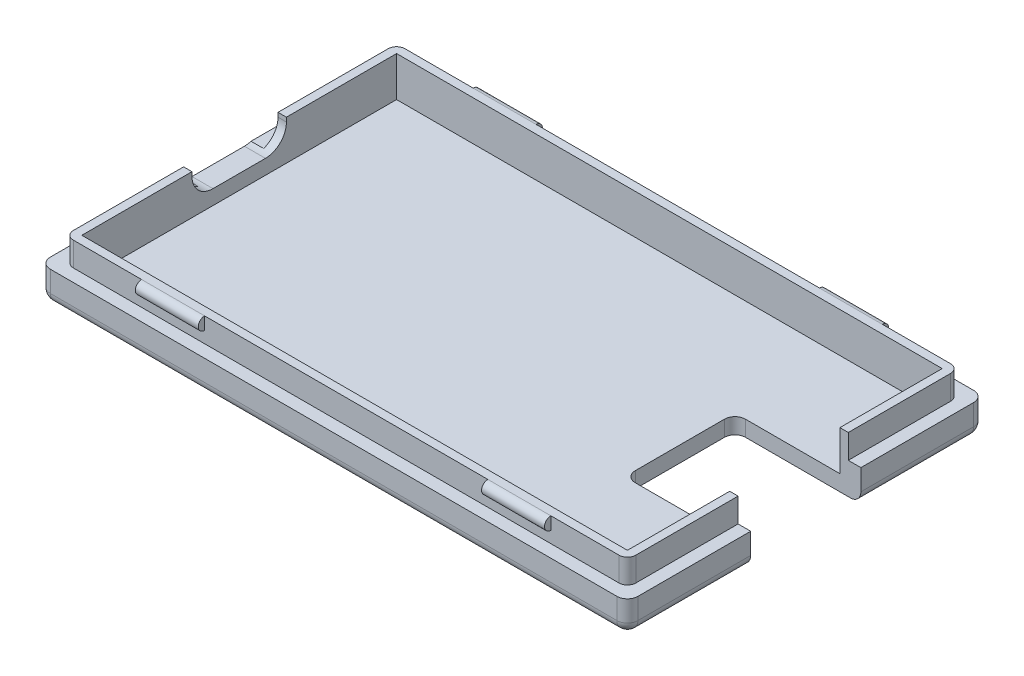
SolidWorks part; units mm, degrees
material "ABS"
ref_plane "Front Plane" through (0, 0, 0) normal (0, 0, 1) x (1, 0, 0)
ref_plane "Top Plane" through (0, 0, 0) normal (0, 1, 0) x (1, 0, 0)
ref_plane "Right Plane" through (0, 0, 0) normal (1, 0, 0) x (0, 0, -1)
sketch "Sketch1" plane through (0, 0, 0) normal (0, 1, 0) x (1, 0, 0)
  line L1 (28, -17) -> (-28, -17)
  line L2 (28, -17) -> (28, 17)
  line L3 (28, 17) -> (-28, 17)
  line L4 (-28, -17) -> (-28, 17)
  line L5 (28, -17) -> (-28, 17) construction
  line L6 (28, 17) -> (-28, -17) construction
  line L7 (26, -15) -> (-26, -15)
  line L8 (26, -15) -> (26, 15)
  line L9 (26, 15) -> (-26, 15)
  line L10 (-26, -15) -> (-26, 15)
  line L11 (26, -15) -> (-26, 15) construction
  line L12 (26, 15) -> (-26, -15) construction
  point P0 (0, 0)
  point P6 (0, 0)
  dimension "D1" = 56
  dimension "D2" = 34
  dimension "D3" = 2
  dimension "D4" = 2
extrude "Base" add sketch "Sketch1" along normal blind 1.5 contours L10 L7 L8 L9 | L4 L1 L2 L3 L7 L10 L9 L8 region at (0, 0, 16.3449) region at (0, 0, 0)
extrude "Boss-Extrude2" add sketch "Sketch1<3>" along normal blind 3 contours L4 L1 L2 L3 L7 L10 L9 L8 region at (0, 0, 16.3449)
sketch "Sketch1<3>" plane through (0, 0, 0) normal (0, 1, 0) x (1, 0, 0) same geometry as "Sketch1"
sketch "Sketch2" plane through (0, 3, 0) normal (0, 1, 0) x (1, 0, 0)
  line L0 (26, 15) -> (26, -15) construction
  line L1 (-26, -15) -> (26, -15) construction
  line L2 (-26, -15) -> (-26, 15) construction
  line L3 (-26, 15) -> (26, 15) construction
  line L4 (26, 15) -> (26, -15)
  line L5 (-26, -15) -> (26, -15)
  line L6 (-26, -15) -> (-26, 15)
  line L7 (-26, 15) -> (26, 15)
  line L8 (-26.8, 15.8) -> (26.8, 15.8)
  line L9 (26.8, 15.8) -> (26.8, -15.8)
  line L10 (-26.8, -15.8) -> (26.8, -15.8)
  line L11 (-26.8, -15.8) -> (-26.8, 15.8)
  dimension "D1" = 0.8
extrude "Wall" add sketch "Sketch2" along normal blind 2.3
sketch "Sketch3" plane through (0, 3, 0) normal (0, 1, 0) x (1, 0, 0)
  line L0 (-28, -17) -> (-28, 17) construction
  line L1 (-28, -10.25) -> (-26.8, -10.25)
  line L2 (-28, -10.25) -> (-28, -6.5)
  line L3 (-28, -6.5) -> (-26.8, -6.5)
  line L4 (-26.8, -10.25) -> (-26.8, -6.5)
  line L5 (-26.8, 15.8) -> (-26.8, -15.8) construction
  line L6 (0, 0) -> (-10.9883, 0) construction
  line L7 (-28, 6.5) -> (-26.8, 6.5)
  line L8 (-26.8, 10.25) -> (-26.8, 6.5)
  line L9 (-28, 10.25) -> (-26.8, 10.25)
  line L10 (-28, 10.25) -> (-28, 6.5)
  dimension "D1" = 13
  dimension "D2" = 20.5
extrude "GrooveForOpen" cut sketch "Sketch3" against normal blind 1
sketch "Sketch4" plane through (0, 0, 0) normal (1, 0, 0) x (0, 0, -1)
  line L0 (15.8, 5.3) -> (15.8, 3) construction
  line L1 (-15.8, 5.3) -> (-15.8, 3) construction
  circle A0 centre (15.8, 4.7) radius 0.6
  circle A1 centre (-15.8, 4.7) radius 0.6
  dimension "D1" = 1.2
extrude "LockPins" add sketch "Sketch4" along normal blind 6 from offset 13.5
mirror "LockPins2" about plane through (0, 0, 0) normal (1, 0, 0) of "LockPins"
fillet "FilletBase" radius 1 8 edges at (0, 0, 17) (28, 0, 0) (0, 0, -17) (-28, 0, 0) (28, 1.5, 17) (-28, 1.5, 17) (-28, 1.5, -17) (28, 1.5, -17)
fillet "FilletInner" radius 0.8 4 edges at (26.8, 4.15, 15.8) (-26.8, 4.15, 15.8) (-26.8, 4.15, -15.8) (26.8, 4.15, -15.8)
sketch "Sketch5" plane through (0, 0, 0) normal (1, 0, 0) x (0, 0, -1)
  line L0 (-15, 5.3) -> (15, 5.3) construction
  line L1 (-4.5, 9.6229) -> (4.5, 9.6229)
  line L2 (-4.5, 9.6229) -> (-4.5, 4.9)
  line L3 (-2.5, 2.9) -> (2.5, 2.9)
  line L4 (4.5, 9.6229) -> (4.5, 4.9)
  arc A0 (2.5, 2.9) -> (4.5, 4.9) centre (2.5, 4.9) ccw
  arc A1 (-4.5, 4.9) -> (-2.5, 2.9) centre (-2.5, 4.9) ccw
  point P4 (0, 9.6229)
  dimension "D2" = 2
  dimension "D1" = 9
  dimension "D3" = 2.4
extrude "CutCable" cut sketch "Sketch5" against normal through all
sketch "Sketch7" plane through (0, 0, 0) normal (0, -1, 0) x (1, 0, 0)
  line L0 (28, 16) -> (28, -16) construction
  line L1 (32.0379, -5.25) -> (17, -5.25)
  line L2 (32.0379, -5.25) -> (32.0379, 5.25)
  line L3 (32.0379, 5.25) -> (17, 5.25)
  line L4 (16, -4.25) -> (16, 4.25)
  line L5 (32.0379, -5.25) -> (16, 5.25) construction
  line L6 (32.0379, 5.25) -> (16, -5.25) construction
  arc A0 (17, -5.25) -> (16, -4.25) centre (17, -4.25) cw
  arc A1 (16, 4.25) -> (17, 5.25) centre (17, 4.25) cw
  point P0 (24.019, 0)
  dimension "D2" = 1
  dimension "D1" = 10.5
  dimension "D3" = 11
extrude "CutForConnector" cut sketch "Sketch7" against normal through all
